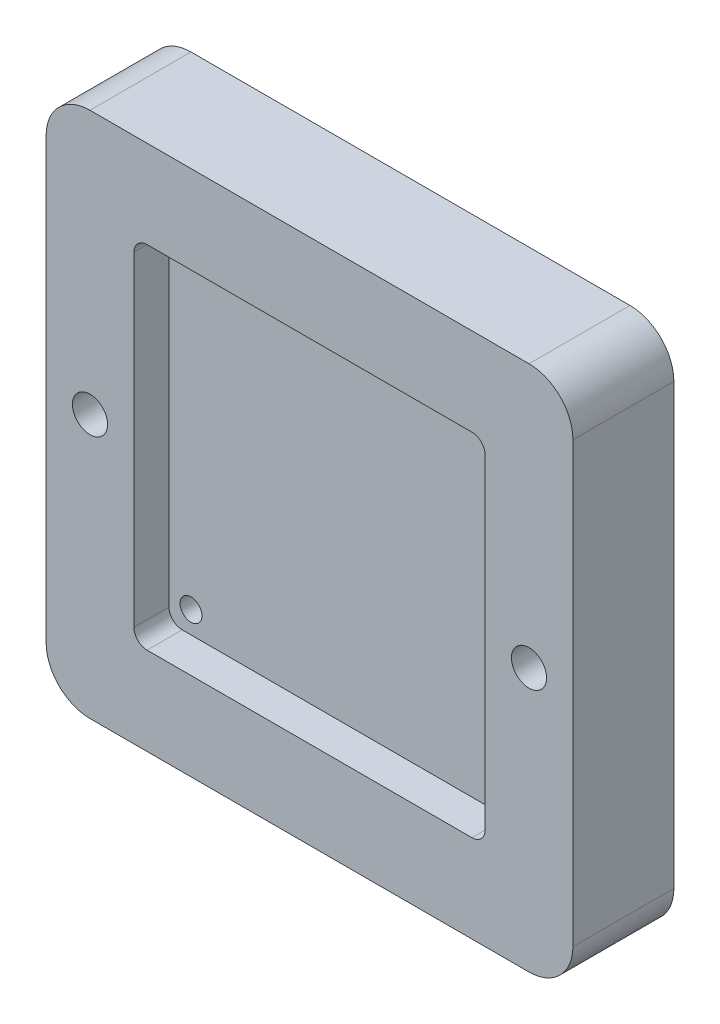
SolidWorks part; units mm, degrees
ref_plane "Front Plane" through (0, 0, 0) normal (0, 0, 1) x (1, 0, 0)
ref_plane "Top Plane" through (0, 0, 0) normal (0, 1, 0) x (1, 0, 0)
ref_plane "Right Plane" through (0, 0, 0) normal (1, 0, 0) x (0, 0, -1)
sketch "Sketch1" plane through (0, 0, 0) normal (0, 0, 1) x (1, 0, 0)
  line L0 (0, 60) -> (0, -60) construction
  line L1 (-50, 60) -> (50, 60)
  line L2 (-60, 50) -> (-60, -50)
  line L3 (-50, -60) -> (50, -60)
  line L4 (60, 50) -> (60, -50)
  line L5 (0, -60) -> (0, -40) construction
  line L6 (0, 40) -> (0, -40) construction
  line L7 (-37, 40) -> (37, 40)
  line L8 (-40, 37) -> (-40, -37)
  line L9 (-37, -40) -> (37, -40)
  line L10 (40, 37) -> (40, -37)
  line L11 (-40, 0) -> (-60, 0) construction
  line L12 (40, 0) -> (60, 0) construction
  arc A0 (50, 60) -> (60, 50) centre (50, 50) cw
  arc A1 (60, -50) -> (50, -60) centre (50, -50) cw
  arc A2 (-50, -60) -> (-60, -50) centre (-50, -50) cw
  arc A3 (-50, 60) -> (-60, 50) centre (-50, 50) ccw
  circle A4 centre (-50, 0) radius 4 construction
  circle A5 centre (50, 0) radius 4 construction
  arc A6 (-40, -37) -> (-37, -40) centre (-37, -37) ccw
  arc A7 (37, -40) -> (40, -37) centre (37, -37) ccw
  arc A8 (40, 37) -> (37, 40) centre (37, 37) ccw
  arc A9 (-37, 40) -> (-40, 37) centre (-37, 37) ccw
  point P31 (111.9206, -20.4692)
  point P32 (50, 0)
  point P39 (-50, 0)
  dimension "D1" = 10
  dimension "D2" = 8
  dimension "D3" = 3
  dimension "D4" = 80
  dimension "D5" = 80
  dimension "D6" = 20
extrude "Boss-Extrude1" add sketch "Sketch1" against normal blind 8
sketch "Sketch2" plane through (0, 0, -8) normal (0, 0, 1) x (1, 0, 0)
  line L8 (-50, -60) -> (50, -60) construction
  line L9 (60, 50) -> (60, -50) construction
  line L10 (-50, 60) -> (50, 60) construction
  line L11 (-60, 50) -> (-60, -50) construction
  line L12 (-50, -60) -> (50, -60)
  line L13 (60, 50) -> (60, -50)
  line L14 (-50, 60) -> (50, 60)
  line L15 (-60, 50) -> (-60, -50)
  arc A8 (50, -60) -> (60, -50) centre (50, -50) ccw construction
  arc A9 (60, 50) -> (50, 60) centre (50, 50) ccw construction
  arc A10 (-50, 60) -> (-60, 50) centre (-50, 50) ccw construction
  arc A11 (-60, -50) -> (-50, -60) centre (-50, -50) ccw construction
  arc A12 (50, -60) -> (60, -50) centre (50, -50) ccw
  arc A13 (60, 50) -> (50, 60) centre (50, 50) ccw
  arc A14 (-50, 60) -> (-60, 50) centre (-50, 50) ccw
  arc A15 (-60, -50) -> (-50, -60) centre (-50, -50) ccw
extrude "Boss-Extrude2" add sketch "Sketch2" against normal blind 15
sketch "Sketch3" plane through (0, 0, 0) normal (0, 0, 1) x (1, 0, 0)
  point P0 (-50, 0)
  point P3 (50, 0)
hole_wizard "Ø8.0mm Dowel Hole1" positions "Sketch3" profile "Sketch4" hole size "Ø8.0" standard "ANSI Metric"
sketch "Sketch4" plane through (-50, 0, 0) normal (1, 0, 0) x (0, -1, 0)
  line L0 (0, 0) -> (0, 20.4034)
  line L1 (0, 20.4034) -> (4, 18)
  line L2 (4, 18) -> (4, 0)
  line L5 (4, 0) -> (0, 0)
  line L10 (0, 20.4034) -> (-4, 18) construction
  line L11 (0, -6.35) -> (0, 107.95) construction
  dimension "Hole Dia." = 8
  dimension "Hole Depth" = 18
  dimension "Drill Angle" = 118
sketch "Sketch5" plane through (0, 0, -8) normal (0, 0, 1) x (1, 0, 0)
  line L0 (-35, 35) -> (35, -35) construction
  line L1 (-35, 35) -> (35, 35) construction
  line L2 (-35, 35) -> (-35, -35) construction
  line L3 (-35, -35) -> (35, -35) construction
  line L4 (35, 35) -> (35, -35) construction
  point P5 (-35, 35)
  point P7 (35, 35)
  point P8 (35, -35)
  point P9 (-35, -35)
  dimension "D1" = 70
sketch "Sketch6" plane through (0, 0, -8) normal (0, 0, 1) x (1, 0, 0)
  point P0 (-35, 35)
  point P3 (35, 35)
  point P6 (35, -35)
  point P9 (-35, -35)
hole_wizard "Tap Drill for M6x1.0 Tap1" positions "Sketch6" profile "Sketch7" hole size "M6x1.0" standard "ANSI Metric"
sketch "Sketch7" plane through (-35, 35, -8) normal (1, 0, 0) x (0, -1, 0)
  line L0 (0, 0) -> (0, 11.5022)
  line L1 (0, 11.5022) -> (2.5, 10)
  line L2 (2.5, 10) -> (2.5, 0)
  line L5 (2.5, 0) -> (0, 0)
  line L10 (0, 11.5022) -> (-2.5, 10) construction
  line L11 (0, -6.35) -> (0, 107.95) construction
  dimension "Hole Dia." = 5
  dimension "Hole Depth" = 10
  dimension "Drill Angle" = 118
